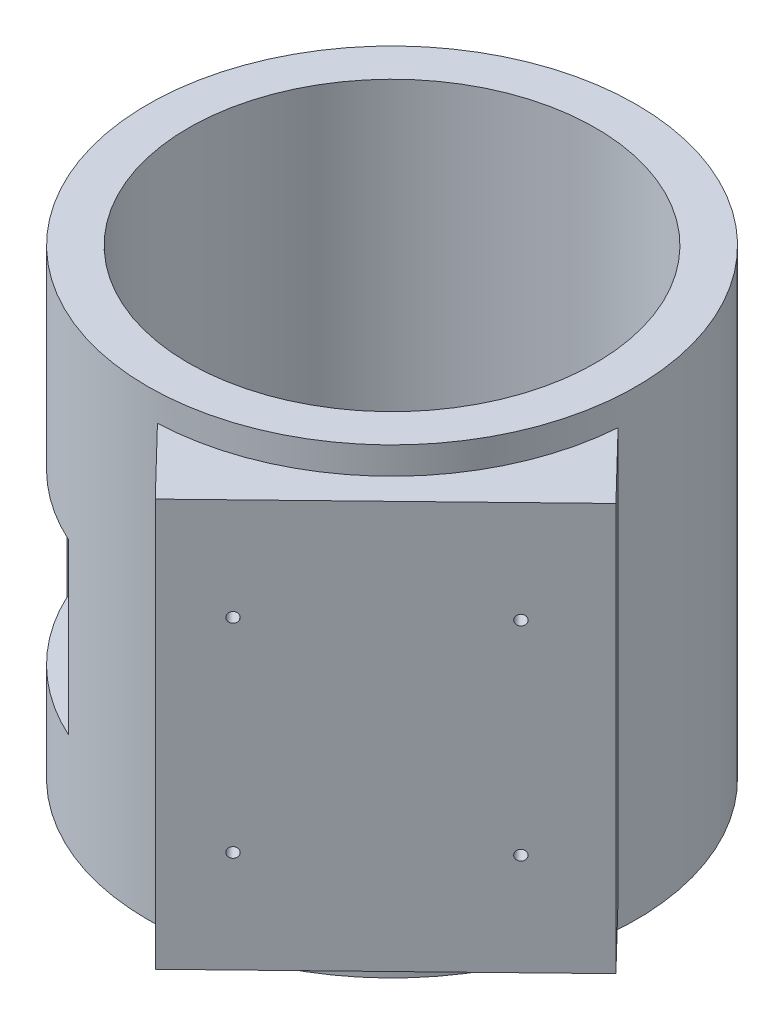
SolidWorks part; units mm, degrees
ref_plane "前视基准面" through (0, 0, 0) normal (0, 0, 1) x (1, 0, 0)
ref_plane "上视基准面" through (0, 0, 0) normal (0, 1, 0) x (1, 0, 0)
ref_plane "右视基准面" through (0, 0, 0) normal (1, 0, 0) x (0, 0, -1)
sketch "草图2" plane through (0, 0, 0) normal (0, 1, 0) x (1, 0, 0)
  circle A0 centre (0, 0) radius 100
  circle A1 centre (0, 0) radius 120
  dimension "D1" = 200
  dimension "D2" = 240
extrude "凸台-拉伸1" add sketch "草图2" along normal blind 226.75
ref_plane "基准面1" through (86.9388, 0, 89.8701) normal (0.6953, 0, 0.7187) x (0.7187, 0, -0.6953)
sketch "草图3" plane through (1112.773, 1150.452, -902.5046) normal (0.6953, 0, 0.7187) x (0.0779, 0.9941, -0.0754)
  line L0 (-1094.5421, 1301.3101) -> (-1273.4815, 1281.799) construction
  line L1 (-1273.4815, 1281.799) -> (-1267.5198, 1227.1231) construction
  line L2 (-1267.5198, 1227.1231) -> (-1088.5804, 1246.6342) construction
  line L3 (-1088.5804, 1246.6342) -> (-1094.5421, 1301.3101) construction
  line L4 (-1276.7333, 1311.6223) -> (-1097.7939, 1331.1333) construction
  line L5 (-1097.7939, 1331.1333) -> (-1103.7556, 1385.8093) construction
  line L6 (-1103.7556, 1385.8093) -> (-1282.6951, 1366.2982) construction
  line L7 (-1282.6951, 1366.2982) -> (-1276.7333, 1311.6223) construction
  line L8 (-1094.5421, 1301.3101) -> (-1273.4815, 1281.799) construction
  line L9 (-1273.4815, 1281.799) -> (-1267.5198, 1227.1231)
  line L10 (-1267.5198, 1227.1231) -> (-1088.5804, 1246.6342)
  line L11 (-1088.5804, 1246.6342) -> (-1094.5421, 1301.3101)
  line L12 (-1276.7333, 1311.6223) -> (-1097.7939, 1331.1333) construction
  line L13 (-1097.7939, 1331.1333) -> (-1103.7556, 1385.8093)
  line L14 (-1103.7556, 1385.8093) -> (-1282.6951, 1366.2982)
  line L15 (-1282.6951, 1366.2982) -> (-1276.7333, 1311.6223)
  line L16 (-1097.7939, 1331.1333) -> (-1094.5421, 1301.3101)
  line L17 (-1273.4815, 1281.799) -> (-1276.7333, 1311.6223)
  line L18 (-1087.8528, 1332.2173) -> (-1094.8985, 1396.8343)
  line L19 (-1094.8985, 1396.8343) -> (-1293.7201, 1375.1553)
  line L20 (-1293.7201, 1375.1553) -> (-1286.6744, 1310.5383)
  line L21 (-1283.4226, 1280.7151) -> (-1286.6744, 1310.5383)
  line L22 (-1283.4226, 1280.7151) -> (-1276.3769, 1216.0981)
  line L23 (-1276.3769, 1216.0981) -> (-1077.5553, 1237.777)
  line L24 (-1077.5553, 1237.777) -> (-1084.601, 1302.394)
  line L25 (-1087.8528, 1332.2173) -> (-1084.601, 1302.394)
  dimension "D1" = 10
extrude "切除-拉伸1" cut sketch "草图3" against normal blind 100 contours L18 L19 L20 L21 L22 L23 L24 L25
sketch "草图4" plane through (1112.773, 1150.452, -902.5046) normal (0.6953, 0, 0.7187) x (0.0779, 0.9941, -0.0754)
  line L0 (-1293.7201, 1375.1553) -> (-1094.8985, 1396.8343) construction
  line L1 (-1276.3769, 1216.0981) -> (-1293.7201, 1375.1553) construction
  line L2 (-1077.5553, 1237.777) -> (-1276.3769, 1216.0981) construction
  line L3 (-1094.8985, 1396.8343) -> (-1077.5553, 1237.777) construction
  line L4 (-1293.7201, 1375.1553) -> (-1094.8985, 1396.8343)
  line L5 (-1276.3769, 1216.0981) -> (-1293.7201, 1375.1553)
  line L6 (-1077.5553, 1237.777) -> (-1276.3769, 1216.0981)
  line L7 (-1094.8985, 1396.8343) -> (-1077.5553, 1237.777)
  line L12 (-1276.7333, 1311.6223) -> (-1097.7939, 1331.1333)
  line L13 (-1097.7939, 1331.1333) -> (-1103.7556, 1385.8093)
  line L14 (-1103.7556, 1385.8093) -> (-1282.6951, 1366.2982)
  line L15 (-1282.6951, 1366.2982) -> (-1276.7333, 1311.6223)
  line L16 (-1276.7333, 1311.6223) -> (-1097.7939, 1331.1333) construction
  line L17 (-1097.7939, 1331.1333) -> (-1103.7556, 1385.8093)
  line L18 (-1103.7556, 1385.8093) -> (-1282.6951, 1366.2982)
  line L19 (-1282.6951, 1366.2982) -> (-1276.7333, 1311.6223)
  line L20 (-1097.7939, 1331.1333) -> (-1094.5421, 1301.3101)
  line L21 (-1276.7333, 1311.6223) -> (-1273.4815, 1281.799)
  line L24 (-1094.5421, 1301.3101) -> (-1273.4815, 1281.799)
  line L25 (-1273.4815, 1281.799) -> (-1267.5198, 1227.1231)
  line L26 (-1267.5198, 1227.1231) -> (-1088.5804, 1246.6342)
  line L27 (-1088.5804, 1246.6342) -> (-1094.5421, 1301.3101)
  line L28 (-1094.5421, 1301.3101) -> (-1273.4815, 1281.799) construction
  line L29 (-1273.4815, 1281.799) -> (-1267.5198, 1227.1231)
  line L30 (-1267.5198, 1227.1231) -> (-1088.5804, 1246.6342)
  line L31 (-1088.5804, 1246.6342) -> (-1094.5421, 1301.3101)
  dimension "D1" = 0
  dimension "D2" = 0
extrude "凸台-拉伸3" add sketch "草图4" against normal up to surface (185.04 mm away) up to face at (55.6231, 113.4142, 57.4985)
sketch "草图5" plane through (0, 213.4142, 0) normal (0, 1, 0) x (1, 0, 0)
  circle A0 centre (0, 0) radius 100 construction
  circle A1 centre (0, 0) radius 100
extrude "切除-拉伸2" cut sketch "草图5" against normal through all both and the other way through all
sketch "草图6" plane through (86.9388, 0, 89.8701) normal (0.6953, 0, 0.7187) x (0.7187, 0, -0.6953)
  line L4 (-80, 13.4142) -> (80, 13.4142)
  line L5 (80, 13.4142) -> (80, 213.4142)
  line L6 (80, 213.4142) -> (-80, 213.4142)
  line L7 (-80, 213.4142) -> (-80, 13.4142)
  line L8 (-80, 13.4142) -> (80, 13.4142)
  line L9 (80, 13.4142) -> (80, 213.4142)
  line L10 (80, 213.4142) -> (-80, 213.4142)
  line L13 (-80, 213.4142) -> (-80, 13.4142)
  dimension "D1" = 0
extrude "凸台-拉伸4" add sketch "草图6" along normal blind 10
sketch "草图7" plane through (93.8917, 0, 97.0574) normal (0.6953, 0, 0.7187) x (0.7187, 0, -0.6953)
  line L4 (70, 203.4142) -> (-70, 203.4142)
  line L6 (70, 203.4142) -> (-70, 203.4142) construction
  line L12 (70, 23.4142) -> (70, 203.4142)
  line L14 (70, 23.4142) -> (70, 203.4142) construction
  line L19 (-70, 23.4142) -> (70, 23.4142)
  line L23 (-70, 23.4142) -> (70, 23.4142) construction
  line L25 (-70, 203.4142) -> (-70, 23.4142)
  line L27 (-70, 203.4142) -> (-70, 23.4142) construction
  circle A0 centre (47, 163.4142) radius 2.5
  circle A1 centre (-53, 163.4142) radius 2.5
  circle A2 centre (-53, 63.4142) radius 2.5
  circle A3 centre (47, 63.4142) radius 2.5
  dimension "D2" = 5
  dimension "D5" = 5
  dimension "D6" = 5
  dimension "D7" = 5
  dimension "D1" = 0
extrude "切除-拉伸4" cut sketch "草图7" against normal up to next contours A0 | A3 | L6 L27 L23 L14 | A1 | A2 region at (127.6721, 163.4142, 64.3789) region at (127.6721, 63.4142, 64.3789)
ref_plane "基准面2" through (0, 0, 0) normal (-0.7187, 0, 0.6953) x (0.6953, 0, 0.7187)
ref_plane "基准面3" through (-86.2477, 0, 83.4346) normal (-0.7187, 0, 0.6953) x (0.6953, 0, 0.7187)
sketch "草图9" plane through (-86.2477, 0, 83.4346) normal (-0.7187, 0, 0.6953) x (0.6953, 0, 0.7187)
  line L9 (2.54, 207.6101) -> (2.54, 62.1309) construction
  line L10 (-120, 0) -> (120, 0) construction
  line L11 (-38.96, 131.41) -> (44.04, 131.41)
  line L12 (-38.96, 131.41) -> (-38.96, 48.41)
  line L13 (-38.96, 48.41) -> (44.04, 48.41)
  line L14 (44.04, 131.41) -> (44.04, 48.41)
  line L15 (-38.96, 131.41) -> (44.04, 48.41) construction
  line L16 (-38.96, 48.41) -> (44.04, 131.41) construction
  point P0 (2.54, 89.91)
  dimension "D1" = 83
  dimension "D2" = 83
  dimension "D3" = 48.41
extrude "切除-拉伸8" cut sketch "草图9" against normal blind 29
sketch "草图10" plane through (0, 0, 0) normal (0, -1, 0) x (1, 0, 0)
  circle A0 centre (-74.9005, 73.5698) radius 5 construction
  circle A1 centre (73.5103, 78.4921) radius 5 construction
  circle A2 centre (78.4326, -69.9187) radius 5 construction
  circle A3 centre (-69.9782, -74.841) radius 5 construction
  circle A4 centre (-74.9005, 73.5698) radius 5
  circle A5 centre (73.5103, 78.4921) radius 5
  circle A6 centre (78.4326, -69.9187) radius 5
  circle A7 centre (-69.9782, -74.841) radius 5
extrude "切除-拉伸9" cut sketch "草图10" against normal blind 20
